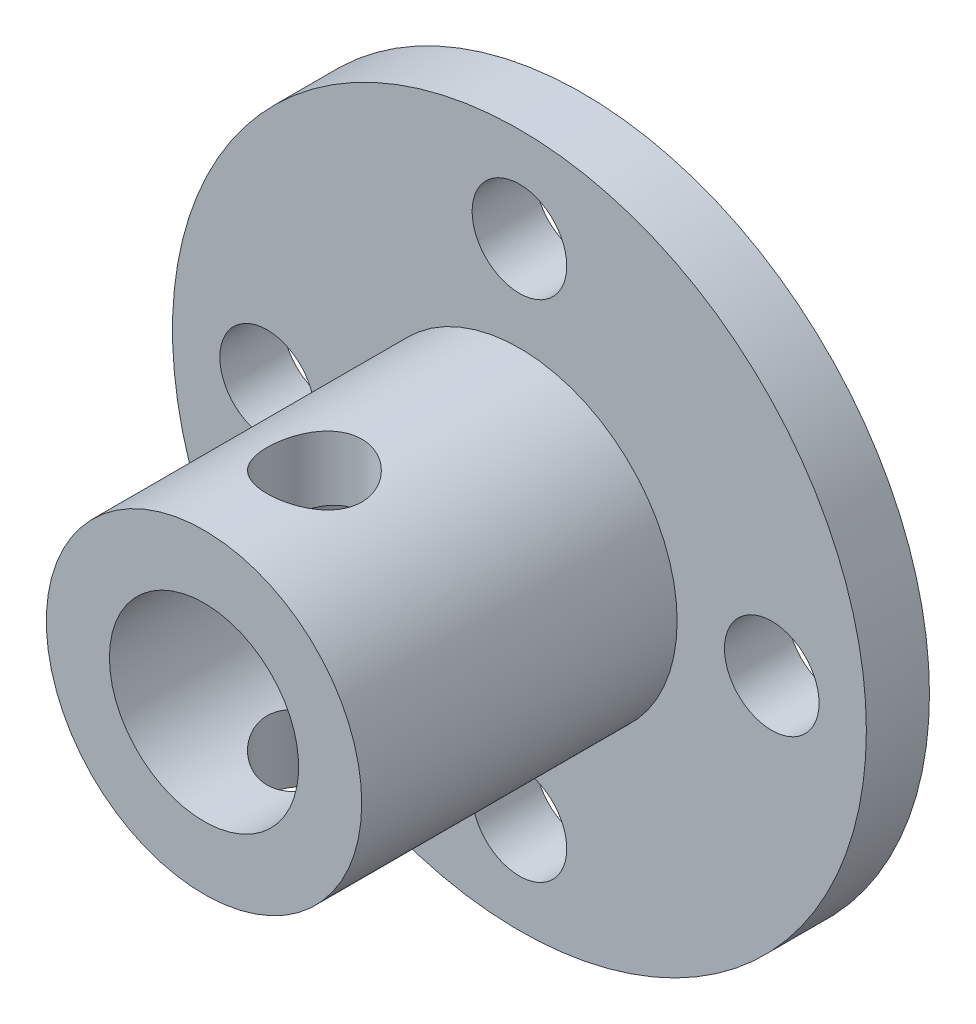
SolidWorks part; units mm, degrees
ref_plane "前视基准面" through (0, 0, 0) normal (0, 0, 1) x (1, 0, 0)
ref_plane "上视基准面" through (0, 0, 0) normal (0, 1, 0) x (1, 0, 0)
ref_plane "右视基准面" through (0, 0, 0) normal (1, 0, 0) x (0, 0, -1)
sketch "草图1" plane through (0, 0, 0) normal (0, 0, 1) x (1, 0, 0)
  circle A0 centre (0, 0) radius 11
extrude "凸台-拉伸1" add sketch "草图1" along normal blind 2
sketch "草图2" plane through (0, 0, 2) normal (0, 0, 1) x (1, 0, 0)
  circle A0 centre (0, 0) radius 5
extrude "凸台-拉伸2" add sketch "草图2" along normal blind 10
sketch "草图3" plane through (0, 0, 0) normal (0, 0, -1) x (-1, 0, 0)
  circle A0 centre (0, 0) radius 3
  circle A1 centre (0, 0) radius 8 construction
  circle A2 centre (0, 8) radius 1.5
  circle A3 centre (8, 0) radius 1.5
  circle A4 centre (0, -8) radius 1.5
  circle A5 centre (-8, 0) radius 1.5
extrude "切除-拉伸1" cut sketch "草图3" against normal blind 12
sketch "草图4" plane through (0, 0, 0) normal (0, 1, 0) x (1, 0, 0)
  line L0 (0, -6.6) -> (0, 6.6) construction
  circle A0 centre (0, -8.5) radius 1.5
extrude "切除-拉伸2" cut sketch "草图4" against normal blind 12 and the other way blind 12
